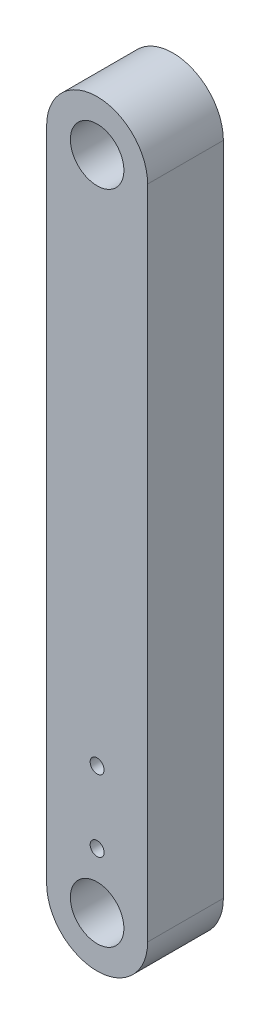
SolidWorks part; units mm, degrees
ref_plane "Front Plane" through (0, 0, 0) normal (0, 0, 1) x (1, 0, 0)
ref_plane "Top Plane" through (0, 0, 0) normal (0, 1, 0) x (1, 0, 0)
ref_plane "Right Plane" through (0, 0, 0) normal (1, 0, 0) x (0, 0, -1)
sketch "Sketch1" plane through (0, 0, 0) normal (0, 0, 1) x (1, 0, 0)
  line L0 (0, 0) -> (0, 82.55) construction
  line L1 (-6.35, 0) -> (-6.35, 82.55)
  line L2 (6.35, 0) -> (6.35, 82.55)
  arc A0 (-6.35, 0) -> (6.35, 0) centre (0, 0) ccw
  arc A1 (6.35, 82.55) -> (-6.35, 82.55) centre (0, 82.55) ccw
  circle A2 centre (0, 82.55) radius 3.3655
  circle A3 centre (0, 0) radius 3.3655
  point P3 (0, 41.275)
  point P12 (0, 0)
  point P13 (4.0261, 5.0644)
  point P14 (0, 0)
  point P15 (0, 0)
  dimension "D2" = 6.35
  dimension "D3" = 6.731
  dimension "D1" = 82.55
extrude "Boss-Extrude1" add sketch "Sketch1" along normal blind 9.525
sketch "Sketch2" plane through (0, 0, 9.525) normal (0, 0, 1) x (1, 0, 0)
  circle A0 centre (0, 7) radius 0.877
  circle A1 centre (0, 16) radius 0.877
  point P4 (0, 0)
  dimension "D3" = 1.754
  dimension "D1" = 7
  dimension "D2" = 16
extrude "Cut-Extrude1" cut sketch "Sketch2" against normal through all
equation "\"tightTol\"= 0.005in"
equation "\"normTol\"= 0.01in"
equation "\"looseTol\"= 0.02in"
equation "\"D3@Sketch1\"=0.25+1.5*\"normTol\""
equation "\"D1@Sketch2\"=7mm"
equation "\"D2@Sketch2\"=16mm"
equation "\"D3@Sketch2\"=1.5mm+\"normTol\""
